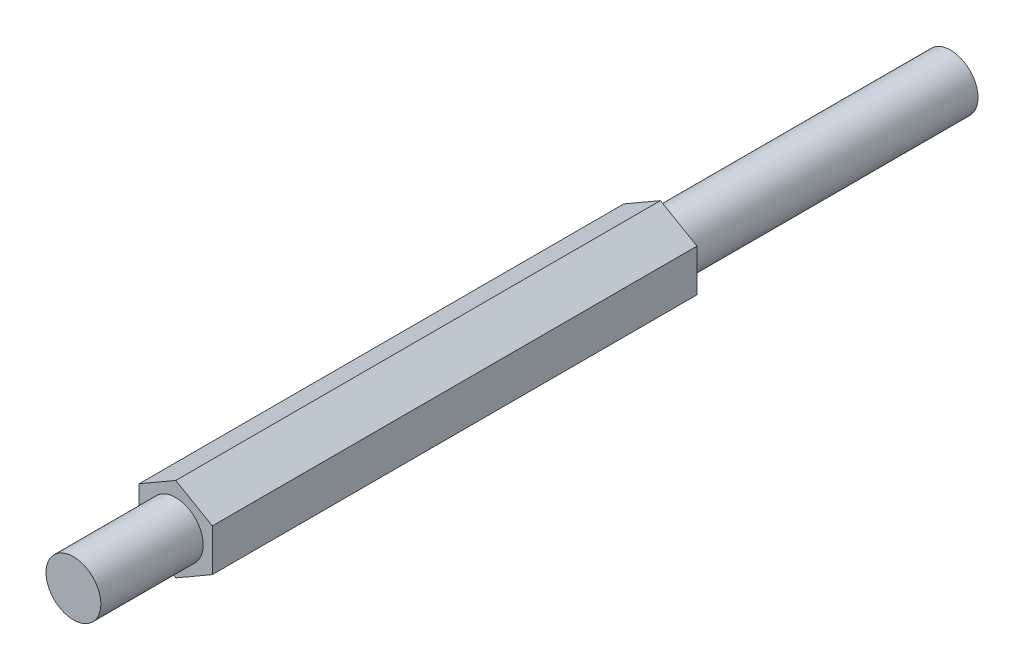
SolidWorks part; units mm, degrees
ref_plane "Front Plane" through (0, 0, 0) normal (0, 0, 1) x (1, 0, 0)
ref_plane "Top Plane" through (0, 0, 0) normal (0, 1, 0) x (1, 0, 0)
ref_plane "Right Plane" through (0, 0, 0) normal (1, 0, 0) x (0, 0, -1)
sketch "Sketch1" plane through (0, 0, 0) normal (0, 0, 1) x (1, 0, 0)
  line L1 (0, -14.6647) -> (12.7, -7.3323)
  line L2 (12.7, -7.3323) -> (12.7, 7.3323)
  line L3 (12.7, 7.3323) -> (0, 14.6647)
  line L4 (0, 14.6647) -> (-12.7, 7.3323)
  line L5 (-12.7, 7.3323) -> (-12.7, -7.3323)
  line L6 (-12.7, -7.3323) -> (0, -14.6647)
  circle A0 centre (0, 0) radius 12.7 construction
  circle A1 centre (0, 0) radius 9.525
  dimension "D2" = 19.05
  dimension "D1" = 25.4
extrude "Boss-Extrude1" add sketch "Sketch1" along normal blind 116.84 and the other way blind 51.562 contours A1 | L5 L6 L1 L2 L3 L4 A1 region at (-6.156, -10.6625, 0) region at (0, 0, 0)
extrude "Boss-Extrude2" add sketch "Sketch1<3>" along normal mid plane 304.8 contours A1 region at (0, 0, 0)
sketch "Sketch1<3>" plane through (0, 0, 0) normal (0, 0, 1) x (1, 0, 0) same geometry as "Sketch1"
